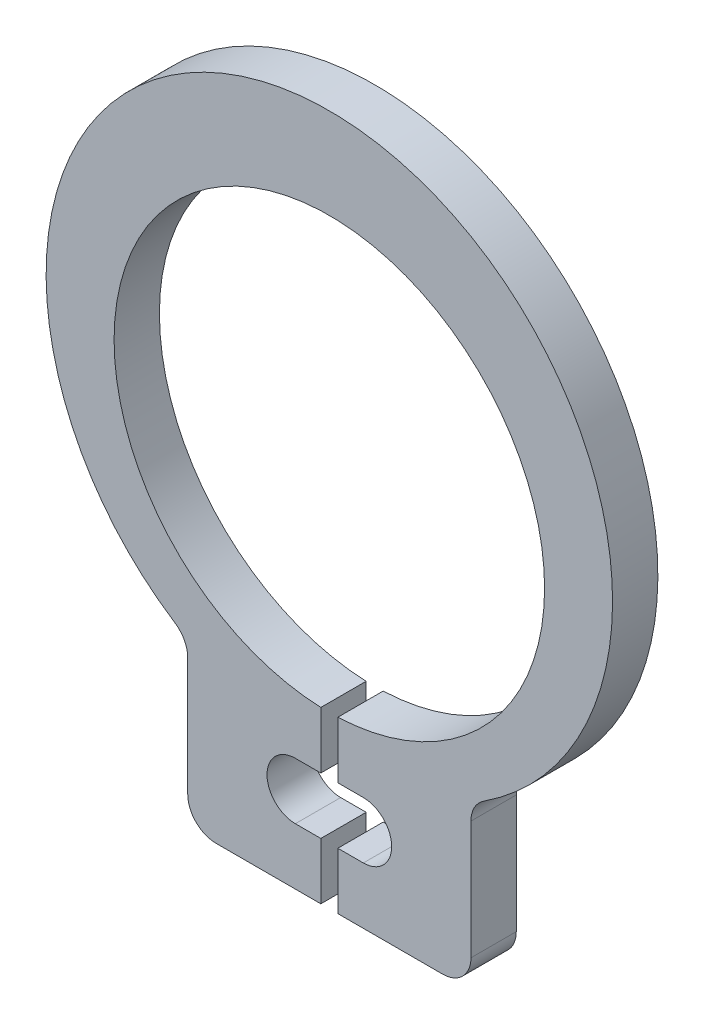
SolidWorks part; units mm, degrees
ref_plane "Front Plane" through (0, 0, 0) normal (0, 0, 1) x (1, 0, 0)
ref_plane "Top Plane" through (0, 0, 0) normal (0, 1, 0) x (1, 0, 0)
ref_plane "Right Plane" through (0, 0, 0) normal (1, 0, 0) x (0, 0, -1)
sketch "Sketch1" plane through (0, 0, 0) normal (0, 0, 1) x (1, 0, 0)
  line L0 (-2.5, -4.2098) -> (-2.5, -6.3)
  line L1 (-2, -6.8) -> (-0.15, -6.8)
  line L5 (-0.15, -6.8) -> (-0.15, -3.797)
  line L6 (0.15, -3.797) -> (0.15, -6.8)
  line L10 (0.15, -6.8) -> (2, -6.8)
  line L11 (2.5, -6.3) -> (2.5, -4.2098)
  line L12 (0, 0) -> (0, 5.4) construction
  arc A0 (2.7273, -3.7907) -> (-2.7273, -3.7907) centre (0, 0.4) ccw
  arc A1 (-2.7273, -3.7907) -> (-2.5, -4.2098) centre (-3, -4.2098) cw
  arc A2 (-2.5, -6.3) -> (-2, -6.8) centre (-2, -6.3) ccw
  arc A4 (-0.15, -3.797) -> (0.15, -3.797) centre (0, 0) cw
  arc A6 (2, -6.8) -> (2.5, -6.3) centre (2, -6.3) ccw
  arc A7 (2.5, -4.2098) -> (2.7273, -3.7907) centre (3, -4.2098) cw
  dimension "D2_s" = 7.6
  dimension "MSM_1" = 10
  dimension "FIX_2" = 0.5
  dimension "FIX_3" = 0.5
  dimension "MSM_2" = 5
  dimension "A_s" = 3
  dimension "FIX_1" = 0.3
  dimension "FIX_4" = 0.4
  dimension "B_s" = 1.6
extrude "Boss-Extrude1" add sketch "Sketch1" along normal blind 0.8
sketch "Sketch2" plane through (0, 0, 0) normal (0, 0, -1) x (-1, 0, 0)
  line L0 (2.5, -5.3) -> (-2.5, -5.3) construction
  line L1 (2.5, -4.2098) -> (2.5, -6.3) construction
  line L2 (-2.5, -6.3) -> (-2.5, -4.2098) construction
  line L3 (2, -6.8) -> (0.15, -6.8) construction
  line L4 (0, 0) -> (0, -6.8) construction
  circle A0 centre (-0.6, -5.3) radius 0.5
  circle A1 centre (0.6, -5.3) radius 0.5
  dimension "D0_s" = 1
  dimension "MSM_4" = 1.5
  dimension "MSM_3" = 1.2
extrude "Cut-Extrude1" cut sketch "Sketch2" against normal through all
other "DeleteFace1" face at (0.625, -5.3, 0.4) face at (-0.625, -5.3, 0.4) and patch yes
sketch "Sketch3" plane through (0, 0, 0) normal (0, 0, -1) x (-1, 0, 0)
  line L0 (2.5, -5.3) -> (-2.5, -5.3) construction
  line L1 (2, -6.8) -> (0.15, -6.8) construction
  line L4 (0, 0) -> (0, -6.8) construction
  line L5 (-0.15, -6.8) -> (-2, -6.8) construction
  line L7 (-0.6, -4.8) -> (0.6, -4.8)
  line L8 (0.6, -5.8) -> (-0.6, -5.8)
  line L9 (2.5, -4.2098) -> (2.5, -6.3) construction
  line L10 (-2.5, -6.3) -> (-2.5, -4.2098) construction
  arc A0 (-0.6, -4.8) -> (-0.6, -5.8) centre (-0.6, -5.3) ccw
  arc A1 (0.6, -5.8) -> (0.6, -4.8) centre (0.6, -5.3) ccw
  dimension "D0_s" = 1
  dimension "MSM_3" = 1.2
  dimension "MSM_4" = 1.5
extrude "Cut-Extrude2" cut sketch "Sketch3" against normal through all
